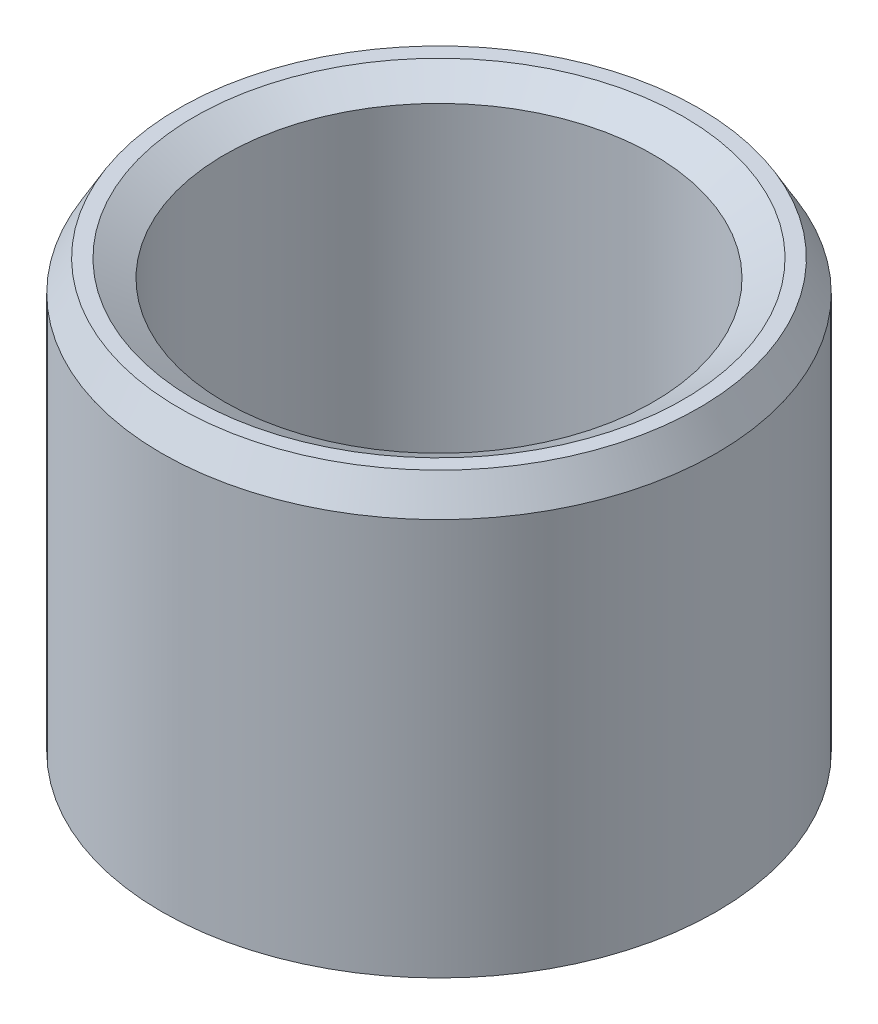
SolidWorks part; units mm, degrees
ref_plane "Front Plane" through (0, 0, 0) normal (0, 0, 1) x (1, 0, 0)
ref_plane "Top Plane" through (0, 0, 0) normal (0, 1, 0) x (1, 0, 0)
ref_plane "Right Plane" through (0, 0, 0) normal (1, 0, 0) x (0, 0, -1)
sketch "Sketch1" plane through (0, 0, 0) normal (0, 1, 0) x (1, 0, 0)
  circle A0 centre (0, 0) radius 15
  dimension "SLEEVE_OD" = 30
extrude "Boss-Extrude1" add sketch "Sketch1" along normal blind 24.0609
sketch "Sketch2" plane through (0, 0, 0) normal (0, 1, 0) x (1, 0, 0)
  circle A0 centre (0, 0) radius 11.5885
  dimension "BORE_D" = 23.1771
extrude "Cut-Extrude1" cut sketch "Sketch2" along normal through all
chamfer "Chamfer1" distance 1.6453 angle 30 4 edges at (0, 24.0609, 11.5885) (0, 0, 11.5885) (0, 0, 15) (0, 24.0609, 15) first distance on face at (0, 24.0609, 11.5885) first distance on face at (0, 0, 11.5885) first distance on face at (0, 24.0609, 15)
